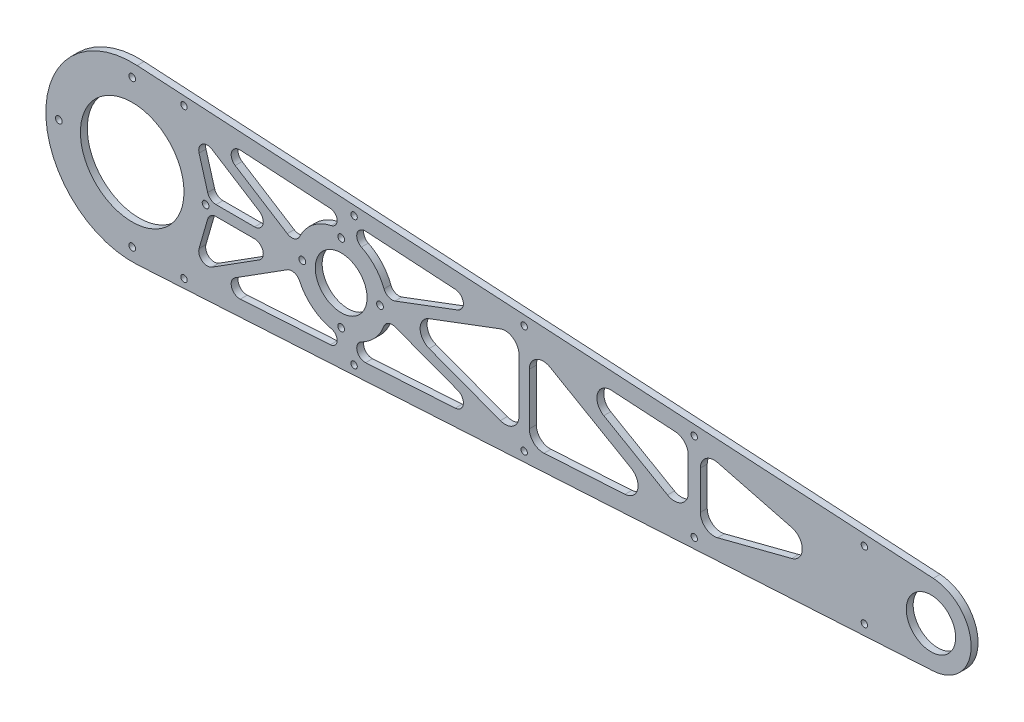
SolidWorks part; units mm, degrees
ref_plane "Front Plane" through (0, 0, 0) normal (0, 0, 1) x (1, 0, 0)
ref_plane "Top Plane" through (0, 0, 0) normal (0, 1, 0) x (1, 0, 0)
ref_plane "Right Plane" through (0, 0, 0) normal (1, 0, 0) x (0, 0, -1)
sketch "Sketch1" plane through (0, 0, 0) normal (0, 0, 1) x (1, 0, 0)
  line L0 (-231.25, 0) -> (231.25, 0) construction
  line L1 (-228.3622, 49.9165) -> (232.595, 23.2486)
  line L2 (-228.3622, -49.9165) -> (232.595, -23.2486)
  line L3 (191.25, 20.6322) -> (-201.25, 43.3396) construction
  circle A0 centre (231.25, 0) radius 14.2875
  arc A1 (232.595, 23.2486) -> (232.595, -23.2486) centre (231.25, 0) cw
  circle A2 centre (-231.25, 0) radius 42.5 construction
  circle A3 centre (-110.25, 0) radius 22.5 construction
  arc A4 (-228.3622, 49.9165) -> (-228.3622, -49.9165) centre (-231.25, 0) ccw
  circle A5 centre (-231.25, 42.5) radius 1.75 construction
  circle A6 centre (-231.25, 0) radius 30
  circle A7 centre (-110.25, 0) radius 15
  circle A8 centre (231.25, 0) radius 35.306 construction
  circle A9 centre (-201.25, 43.3396) radius 1.85
  circle A10 centre (-102.7635, 37.3743) radius 1.85
  circle A11 centre (-4.277, 31.4089) radius 1.85
  circle A12 centre (94.2095, 25.4436) radius 1.85
  circle A13 centre (192.696, 19.4782) radius 1.85
  circle A14 centre (291.1825, 13.5129) radius 1.85 construction
  circle A15 centre (192.696, -19.4782) radius 1.85
  circle A16 centre (94.2095, -25.4436) radius 1.85
  circle A17 centre (-4.277, -31.4089) radius 1.85
  circle A18 centre (-102.7635, -37.3743) radius 1.85
  circle A19 centre (-201.25, -43.3396) radius 1.85
  point P4 (0, 0)
  point P15 (-231.25, 44.25)
  point P16 (-273.75, 0)
  point P17 (-231.25, 50)
  point P18 (-110.25, 22.5)
  point P19 (-231.25, -42.5)
  point P20 (-188.75, 0)
  point P21 (-132.75, 0)
  point P22 (-110.25, -22.5)
  point P23 (-87.75, 0)
  dimension "D2" = 28.575
  dimension "D3" = 85
  dimension "D5" = 45
  dimension "D6" = 3.5
  dimension "D7" = 7.5
  dimension "D8" = 9
  dimension "D9" = 60
  dimension "D10" = 30
  dimension "D11" = 70.612
  dimension "D13" = 3.7
  dimension "D16" = 6
  dimension "D1" = 462.5
  dimension "D4" = 121
  dimension "D12" = 5
  dimension "D14" = 30
  dimension "D15" = 40
extrude "Boss-Extrude1" add sketch "Sketch1" along normal blind 4
sketch "Sketch4" plane through (0, 0, 4) normal (0, 0, 1) x (1, 0, 0)
  point P0 (-231.25, 42.5)
  point P7 (-188.75, 0)
  point P10 (-132.75, 0)
  point P13 (-110.25, 22.5)
  point P16 (-87.75, 0)
  point P19 (-110.25, -22.5)
  point P24 (-273.75, 0)
  point P28 (-231.25, -42.5)
hole_wizard "M3.5 Clearance Hole1" positions "Sketch4" profile "Sketch6" hole size "M3.5" standard "ANSI Metric" end condition up to next
sketch "Sketch6" plane through (-231.25, 42.5, 4) normal (1, 0, 0) x (0, -1, 0)
  line L0 (0, 0) -> (0, 4)
  line L1 (0, 4) -> (1.95, 4)
  line L2 (1.95, 4) -> (1.95, 0)
  line L5 (1.95, 0) -> (0, 0)
  line L11 (0, -6.35) -> (0, 107.95) construction
  dimension "Thru Hole Dia." = 3.9
  dimension "Thru Hole Depth" = 4
sketch "Sketch7" plane through (0, 0, 4) normal (0, 0, 1) x (1, 0, 0)
  line L0 (94.2095, 25.4436) -> (94.2095, -25.4436) construction
  line L1 (94.2095, -25.4436) -> (192.696, 0) construction
  line L2 (192.696, 0) -> (94.2095, 25.4436) construction
  line L3 (192.696, 0) -> (-87.75, 0) construction
  line L4 (192.696, -19.4782) -> (192.696, 19.4782) construction
  line L5 (107.7105, 18.8571) -> (150.7205, 7.7457)
  line L6 (150.7205, -7.7457) -> (107.7105, -18.8571)
  line L7 (97.7095, -11.1115) -> (97.7095, 11.1115)
  line L8 (-4.277, -31.4089) -> (-4.277, 31.4089) construction
  line L9 (-4.277, 31.4089) -> (94.2095, -25.4436) construction
  line L10 (-4.277, 31.4089) -> (94.2095, 25.4436) construction
  line L11 (-4.277, -31.4089) -> (94.2095, -25.4436) construction
  line L12 (-87.75, 0) -> (-102.7635, 37.3743) construction
  line L13 (-102.7635, 37.3743) -> (-4.277, 31.4089) construction
  line L14 (-4.277, 31.4089) -> (-87.75, 0) construction
  line L15 (90.7095, -4.9492) -> (90.7095, 14.1182)
  line L16 (83.1932, 22.1035) -> (46.2904, 24.3387)
  line L17 (41.8072, 9.4249) -> (78.7099, -11.8777)
  line L18 (10.7225, 18.1316) -> (57.6374, -8.9506)
  line L19 (54.1216, -23.8644) -> (7.2067, -26.706)
  line L20 (-1.277, -18.7207) -> (-1.277, 11.2032)
  line L22 (-228.3622, -49.9165) -> (232.595, -23.2486) construction
  line L23 (-7.277, -15.517) -> (-7.277, 15.517)
  line L24 (-18.0944, 23.0044) -> (-59.3325, 7.4875)
  line L25 (-59.3325, -7.4875) -> (-18.0944, -23.0044)
  line L27 (-79.0341, 6.4849) -> (-42.7227, 20.1481)
  line L28 (-44.1812, 29.8186) -> (-96.0994, 32.9633)
  line L32 (-132.75, 0) -> (-188.75, 0) construction
  line L33 (-188.75, 0) -> (-201.25, 43.3396) construction
  line L34 (-201.25, 43.3396) -> (-132.75, 0) construction
  line L35 (-132.75, 0) -> (-102.7635, 37.3743) construction
  line L36 (-102.7635, 37.3743) -> (-201.25, 43.3396) construction
  line L37 (-171.617, 28.141) -> (-141.4788, 9.0727)
  line L39 (-116.5248, 34.2005) -> (-168.6414, 37.3572)
  line L40 (-192.5297, 23.9304) -> (-187.5354, 6.6144)
  line L41 (-182.7313, 3) -> (-160.3569, 3)
  line L42 (-157.6835, 12.2253) -> (-185.0522, 29.5413)
  line L44 (-116.5248, -34.2005) -> (-168.6414, -37.3572)
  line L45 (-171.617, -28.141) -> (-141.4788, -9.0727)
  line L46 (-157.6835, -12.2253) -> (-185.0522, -29.5413)
  line L47 (-192.5297, -23.9304) -> (-187.5354, -6.6144)
  line L48 (-182.7313, -3) -> (-160.3569, -3)
  line L50 (-44.1812, -29.8186) -> (-96.0994, -32.9633)
  line L51 (-79.0341, -6.4849) -> (-42.7227, -20.1481)
  line L52 (-102.7635, -37.3743) -> (-110.25, -22.5) construction
  line L53 (-113.0228, -28.1124) -> (-105.6224, -42.8156) construction
  line L54 (-100.7253, -30.3024) -> (-94.7439, -42.1863) construction
  arc A0 (150.7205, 7.7457) -> (150.7205, -7.7457) centre (148.7195, 0) cw
  arc A1 (107.7105, -18.8571) -> (97.7095, -11.1115) centre (105.7095, -11.1115) cw
  arc A2 (107.7105, 18.8571) -> (97.7095, 11.1115) centre (105.7095, 11.1115) ccw
  arc A3 (90.7095, 14.1182) -> (83.1932, 22.1035) centre (82.7095, 14.1182) ccw
  arc A4 (46.2904, 24.3387) -> (41.8072, 9.4249) centre (45.8067, 16.3534) ccw
  arc A5 (90.7095, -4.9492) -> (78.7099, -11.8777) centre (82.7095, -4.9492) cw
  arc A6 (57.6374, -8.9506) -> (54.1216, -23.8644) centre (53.6379, -15.879) cw
  arc A7 (7.2067, -26.706) -> (-1.277, -18.7207) centre (6.723, -18.7207) cw
  arc A8 (10.7225, 18.1316) -> (-1.277, 11.2032) centre (6.723, 11.2032) ccw
  arc A9 (-7.277, -15.517) -> (-18.0944, -23.0044) centre (-15.277, -15.517) cw
  arc A10 (-7.277, 15.517) -> (-18.0944, 23.0044) centre (-15.277, 15.517) ccw
  arc A11 (-59.3325, 7.4875) -> (-59.3325, -7.4875) centre (-56.5152, 0) ccw
  arc A12 (-42.7227, 20.1481) -> (-44.1812, 29.8186) centre (-44.4835, 24.8278) ccw
  arc A18 (-171.617, 28.141) -> (-168.6414, 37.3572) centre (-168.9437, 32.3663) cw
  arc A21 (-160.3569, 3) -> (-157.6835, 12.2253) centre (-160.3569, 8) ccw
  arc A22 (-187.5354, 6.6144) -> (-182.7313, 3) centre (-182.7313, 8) ccw
  arc A23 (-192.5297, 23.9304) -> (-185.0522, 29.5413) centre (-187.7255, 25.316) cw
  arc A26 (-171.617, -28.141) -> (-168.6414, -37.3572) centre (-168.9437, -32.3663) ccw
  arc A27 (-192.5297, -23.9304) -> (-185.0522, -29.5413) centre (-187.7255, -25.316) ccw
  arc A28 (-187.5354, -6.6144) -> (-182.7313, -3) centre (-182.7313, -8) cw
  arc A29 (-160.3569, -3) -> (-157.6835, -12.2253) centre (-160.3569, -8) cw
  circle A30 centre (-110.25, 0) radius 15 construction
  circle A31 centre (-110.25, 0) radius 15 construction
  circle A32 centre (-110.25, 0) radius 22.5 construction
  arc A34 (-85.4703, 9.3925) -> (-98.5366, 23.7707) centre (-110.25, 0) ccw
  arc A37 (-85.4703, 9.3925) -> (-79.0341, 6.4849) centre (-80.7949, 11.1646) ccw
  arc A38 (-42.7227, -20.1481) -> (-44.1812, -29.8186) centre (-44.4835, -24.8278) cw
  arc A39 (-96.0994, -32.9633) -> (-98.5366, -23.7707) centre (-96.3927, -28.1217) cw
  arc A40 (-134.2728, 11.1872) -> (-115.8848, 25.894) centre (-110.25, 0) cw
  arc A41 (-85.4703, -9.3925) -> (-98.5366, -23.7707) centre (-110.25, 0) cw
  arc A42 (-85.4703, -9.3925) -> (-79.0341, -6.4849) centre (-80.7949, -11.1646) cw
  arc A43 (-116.5248, 34.2005) -> (-115.8848, 25.894) centre (-116.779, 30.003) cw
  arc A44 (-134.2728, 11.1872) -> (-141.4788, 9.0727) centre (-138.8054, 13.298) cw
  arc A45 (-116.5248, -34.2005) -> (-115.8848, -25.894) centre (-116.779, -30.003) ccw
  arc A46 (-134.2728, -11.1872) -> (-115.8848, -25.894) centre (-110.25, 0) ccw
  arc A47 (-134.2728, -11.1872) -> (-141.4788, -9.0727) centre (-138.8054, -13.298) ccw
  arc A48 (-96.0994, 32.9633) -> (-98.5366, 23.7707) centre (-96.3927, 28.1217) ccw
  circle A49 centre (-4.277, -31.4089) radius 1.85 construction
  circle A50 centre (-4.277, -31.4089) radius 1.85
  point P36 (180.7024, 0)
  point P59 (-79.2314, 0)
  point P102 (-113.0228, -28.1124)
  dimension "D8" = 8
  dimension "D11" = 5
  dimension "D12" = 5
  dimension "D18" = 5
  dimension "D19" = 5
  dimension "D10" = 4
  dimension "D21" = 5
  dimension "D1" = 3
  dimension "D2" = 7
  dimension "D3" = 8
  dimension "D4" = 8
  dimension "D5" = 8
  dimension "D6" = 6
  dimension "D7" = 6
  dimension "D9" = 8
  dimension "D13" = 8
  dimension "D14" = 5
  dimension "D15" = 6
  dimension "D16" = 3
  dimension "D17" = 6
extrude "Cut-Extrude1" cut sketch "Sketch7" against normal blind 10
